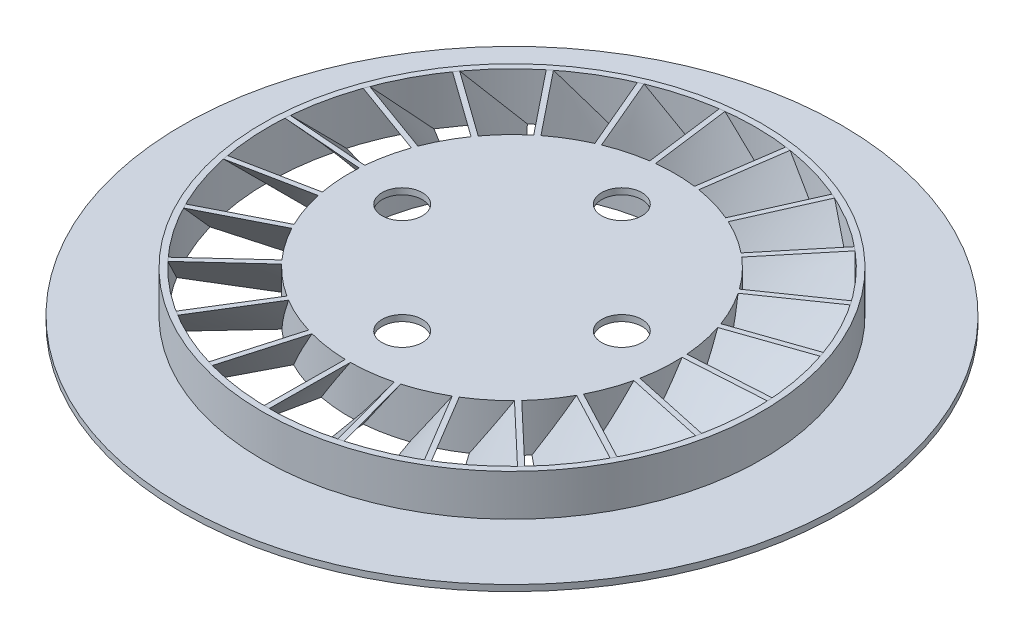
SolidWorks part; units mm, degrees
ref_plane "Front Plane" through (0, 0, 0) normal (0, 0, 1) x (1, 0, 0)
ref_plane "Top Plane" through (0, 0, 0) normal (0, 1, 0) x (1, 0, 0)
ref_plane "Right Plane" through (0, 0, 0) normal (1, 0, 0) x (0, 0, -1)
sketch "Sketch1" plane through (0, 0, 0) normal (0, 1, 0) x (1, 0, 0)
  circle A0 centre (0, 0) radius 33.25
  circle A1 centre (0, 0) radius 34.0882
  circle A2 centre (0, 0) radius 45
  circle A3 centre (0, 0) radius 22.25
  circle A4 centre (0, 0) radius 21.4118
  dimension "D1" = 66.5
  dimension "D2" = 0.8382
  dimension "D3" = 90
  dimension "D4" = 44.5
  dimension "D5" = 0.8382
extrude "Boss-Extrude1" add sketch "Sketch1" along normal blind 6.5 contours A1 A0 region at (-33.9918, 0, 0)
extrude "Boss-Extrude2" add sketch "Sketch1<3>" along normal blind 0.8382 contours A2 A1 region at (-43.7272, 0, 0)
sketch "Sketch1<3>" plane through (0, 0, 0) normal (0, 1, 0) x (1, 0, 0) same geometry as "Sketch1"
extrude "Boss-Extrude3" add sketch "Sketch1<4>" along normal blind 6.5 separate body contours A3 A4 region at (-21.6207, 0, 0)
sketch "Sketch1<4>" plane through (0, 0, 0) normal (0, 1, 0) x (1, 0, 0) same geometry as "Sketch1"
extrude "Boss-Extrude4" add sketch "Sketch1<5>" along normal blind 0.7 contours A4 region at (0, 0, 0)
sketch "Sketch1<5>" plane through (0, 0, 0) normal (0, 1, 0) x (1, 0, 0) same geometry as "Sketch1"
sketch "Sketch2" plane through (0, 0, 0) normal (0, -1, 0) x (1, 0, 0)
  line L0 (-31.9208, 9.3073) -> (-21.3278, 6.3393)
  line L1 (-33.2482, 0.35) -> (-22.2472, 0.35)
  line L2 (-33.2482, -0.35) -> (-22.2472, -0.35)
  line L3 (-32.1097, 8.6332) -> (-21.5167, 5.6652)
  line L4 (-28.226, 17.5743) -> (-18.8266, 11.8584)
  line L5 (-28.5897, 16.9762) -> (-19.1903, 11.2603)
  line L6 (-22.4378, 24.5378) -> (-14.9291, 16.498)
  line L7 (-22.9494, 24.0601) -> (-15.4407, 16.0202)
  line L8 (-14.9856, 29.6816) -> (-9.9244, 19.914)
  line L9 (-15.6071, 29.3595) -> (-10.5459, 19.592)
  line L10 (-6.4219, 32.624) -> (-4.1837, 21.8531)
  line L11 (-7.1072, 32.4815) -> (-4.869, 21.7107)
  line L12 (2.6181, 33.1468) -> (1.8674, 22.1715)
  line L13 (1.9198, 33.1945) -> (1.169, 22.2193)
  line L14 (11.4639, 31.2112) -> (7.7799, 20.8455)
  line L15 (10.8043, 31.4456) -> (7.1204, 21.0799)
  line L16 (19.4595, 26.9609) -> (13.1155, 17.9735)
  line L17 (18.8876, 27.3646) -> (12.5436, 18.3772)
  line L18 (26.0119, 20.711) -> (17.4783, 13.7685)
  line L19 (25.5701, 21.254) -> (17.0366, 14.3115)
  line L20 (30.635, 12.9251) -> (20.5449, 8.5423)
  line L21 (30.3561, 13.5671) -> (20.266, 9.1844)
  line L22 (32.9861, 4.1806) -> (22.0877, 2.6826)
  line L23 (32.8908, 4.874) -> (21.9924, 3.3761)
  line L24 (32.8908, -4.874) -> (21.9924, -3.3761)
  line L25 (32.9861, -4.1806) -> (22.0877, -2.6826)
  line L26 (30.3561, -13.5671) -> (20.266, -9.1844)
  line L27 (30.635, -12.9251) -> (20.5449, -8.5423)
  line L28 (25.5701, -21.254) -> (17.0366, -14.3115)
  line L29 (26.0119, -20.711) -> (17.4783, -13.7685)
  line L30 (18.8876, -27.3646) -> (12.5436, -18.3772)
  line L31 (19.4595, -26.9609) -> (13.1155, -17.9735)
  line L32 (10.8043, -31.4456) -> (7.1204, -21.0799)
  line L33 (11.4639, -31.2112) -> (7.7799, -20.8455)
  line L34 (1.9198, -33.1945) -> (1.169, -22.2193)
  line L35 (2.6181, -33.1468) -> (1.8674, -22.1715)
  line L36 (-7.1072, -32.4815) -> (-4.869, -21.7107)
  line L37 (-6.4219, -32.624) -> (-4.1837, -21.8531)
  line L38 (-15.6071, -29.3595) -> (-10.5459, -19.592)
  line L39 (-14.9856, -29.6816) -> (-9.9244, -19.914)
  line L40 (-22.9494, -24.0601) -> (-15.4407, -16.0202)
  line L41 (-22.4378, -24.5378) -> (-14.9291, -16.498)
  line L42 (-28.5897, -16.9762) -> (-19.1903, -11.2603)
  line L43 (-28.226, -17.5743) -> (-18.8266, -11.8584)
  line L44 (-32.1097, -8.6332) -> (-21.5167, -5.6652)
  line L45 (-31.9208, -9.3073) -> (-21.3278, -6.3393)
  circle A0 centre (0, 0) radius 33.25 construction
  circle A1 centre (0, 0) radius 22.25
  arc A2 (-21.3278, 6.3393) -> (-21.5167, 5.6652) centre (0, 0) ccw
  arc A3 (-18.8266, 11.8584) -> (-19.1903, 11.2603) centre (0, 0) ccw
  circle A5 centre (0, 0) radius 22.25 construction
  arc A6 (-31.9208, 9.3073) -> (-32.1097, 8.6332) centre (0, 0) ccw
  arc A7 (-28.226, 17.5743) -> (-28.5897, 16.9762) centre (0, 0) ccw
  arc A8 (-22.4378, 24.5378) -> (-22.9494, 24.0601) centre (0, 0) ccw
  arc A9 (-14.9291, 16.498) -> (-15.4407, 16.0202) centre (0, 0) ccw
  arc A10 (-9.9244, 19.914) -> (-10.5459, 19.592) centre (0, 0) ccw
  arc A11 (-14.9856, 29.6816) -> (-15.6071, 29.3595) centre (0, 0) ccw
  arc A12 (-6.4219, 32.624) -> (-7.1072, 32.4815) centre (0, 0) ccw
  arc A13 (-4.1837, 21.8531) -> (-4.869, 21.7107) centre (0, 0) ccw
  arc A14 (1.8674, 22.1715) -> (1.169, 22.2193) centre (0, 0) ccw
  arc A15 (2.6181, 33.1468) -> (1.9198, 33.1945) centre (0, 0) ccw
  arc A16 (11.4639, 31.2112) -> (10.8043, 31.4456) centre (0, 0) ccw
  arc A17 (7.7799, 20.8455) -> (7.1204, 21.0799) centre (0, 0) ccw
  arc A18 (13.1155, 17.9735) -> (12.5436, 18.3772) centre (0, 0) ccw
  arc A19 (19.4595, 26.9609) -> (18.8876, 27.3646) centre (0, 0) ccw
  arc A20 (26.0119, 20.711) -> (25.5701, 21.254) centre (0, 0) ccw
  arc A21 (17.4783, 13.7685) -> (17.0366, 14.3115) centre (0, 0) ccw
  arc A22 (20.5449, 8.5423) -> (20.266, 9.1844) centre (0, 0) ccw
  arc A23 (30.635, 12.9251) -> (30.3561, 13.5671) centre (0, 0) ccw
  arc A24 (32.9861, 4.1806) -> (32.8908, 4.874) centre (0, 0) ccw
  arc A25 (22.0877, 2.6826) -> (21.9924, 3.3761) centre (0, 0) ccw
  arc A26 (21.9924, -3.3761) -> (22.0877, -2.6826) centre (0, 0) ccw
  arc A27 (32.8908, -4.874) -> (32.9861, -4.1806) centre (0, 0) ccw
  arc A28 (-22.2472, 0.35) -> (-22.2472, -0.35) centre (0, 0) ccw
  arc A29 (-33.2482, 0.35) -> (-33.2482, -0.35) centre (0, 0) ccw
  arc A30 (-21.5167, -5.6652) -> (-21.3278, -6.3393) centre (0, 0) ccw
  arc A31 (-32.1097, -8.6332) -> (-31.9208, -9.3073) centre (0, 0) ccw
  arc A32 (-19.1903, -11.2603) -> (-18.8266, -11.8584) centre (0, 0) ccw
  arc A33 (-28.5897, -16.9762) -> (-28.226, -17.5743) centre (0, 0) ccw
  arc A34 (-22.9494, -24.0601) -> (-22.4378, -24.5378) centre (0, 0) ccw
  arc A35 (-15.4407, -16.0202) -> (-14.9291, -16.498) centre (0, 0) ccw
  arc A36 (-10.5459, -19.592) -> (-9.9244, -19.914) centre (0, 0) ccw
  arc A37 (-15.6071, -29.3595) -> (-14.9856, -29.6816) centre (0, 0) ccw
  arc A38 (-7.1072, -32.4815) -> (-6.4219, -32.624) centre (0, 0) ccw
  arc A39 (-4.869, -21.7107) -> (-4.1837, -21.8531) centre (0, 0) ccw
  arc A40 (1.169, -22.2193) -> (1.8674, -22.1715) centre (0, 0) ccw
  arc A41 (1.9198, -33.1945) -> (2.6181, -33.1468) centre (0, 0) ccw
  arc A42 (10.8043, -31.4456) -> (11.4639, -31.2112) centre (0, 0) ccw
  arc A43 (7.1204, -21.0799) -> (7.7799, -20.8455) centre (0, 0) ccw
  arc A44 (12.5436, -18.3772) -> (13.1155, -17.9735) centre (0, 0) ccw
  arc A45 (18.8876, -27.3646) -> (19.4595, -26.9609) centre (0, 0) ccw
  arc A46 (25.5701, -21.254) -> (26.0119, -20.711) centre (0, 0) ccw
  arc A47 (17.0366, -14.3115) -> (17.4783, -13.7685) centre (0, 0) ccw
  arc A48 (20.266, -9.1844) -> (20.5449, -8.5423) centre (0, 0) ccw
  arc A49 (30.3561, -13.5671) -> (30.635, -12.9251) centre (0, 0) ccw
  point P106 (0, 0)
  dimension "D3" = 0.7
  dimension "D1" = 0
  dimension "D4" = 23
sketch "Sketch3" plane through (0, 6.5, 0) normal (0, 1, 0) x (1, 0, 0)
  line L0 (0, 0) -> (-32.6054, -6.5152) construction
  line L1 (0, 0) -> (-15.6581, 0) construction
  line L2 (-21.8846, -4.016) -> (-32.6722, -6.1716)
  line L3 (-21.7474, -4.7025) -> (-32.535, -6.8581)
  line L4 (-22.1565, 2.0373) -> (-33.1257, 2.8721)
  line L5 (-22.2097, 1.3393) -> (-33.1788, 2.1741)
  line L6 (-20.7853, 7.9395) -> (-31.1225, 11.7028)
  line L7 (-21.0247, 7.2817) -> (-31.3619, 11.045)
  line L8 (-17.8724, 13.2529) -> (-26.811, 19.6656)
  line L9 (-18.2805, 12.6841) -> (-27.219, 19.0968)
  line L10 (-13.6341, 17.5833) -> (-20.511, 26.1698)
  line L11 (-14.1805, 17.1457) -> (-21.0574, 25.7322)
  line L12 (-8.3846, 20.6097) -> (-12.6899, 30.7332)
  line L13 (-9.0288, 20.3358) -> (-13.3341, 30.4592)
  line L14 (-2.5132, 22.1076) -> (-3.9276, 33.0172)
  line L15 (-3.2074, 22.0176) -> (-4.6218, 32.9272)
  line L16 (3.5445, 21.9659) -> (5.126, 32.8525)
  line L17 (2.8518, 22.0665) -> (4.4332, 32.9531)
  line L18 (9.3394, 20.195) -> (13.7994, 30.2513)
  line L19 (8.6995, 20.4788) -> (13.1595, 30.5351)
  line L20 (14.4416, 16.9264) -> (21.4494, 25.4064)
  line L21 (13.902, 17.3723) -> (20.9098, 25.8524)
  line L22 (18.4728, 12.4024) -> (27.5085, 18.6773)
  line L23 (18.0735, 12.9774) -> (27.1093, 19.2523)
  line L24 (21.1339, 6.9586) -> (31.5275, 10.563)
  line L25 (20.9045, 7.6199) -> (31.2982, 11.2244)
  line L26 (22.2276, 0.9987) -> (33.2083, 1.6653)
  line L27 (22.1852, 1.6974) -> (33.1659, 2.364)
  line L28 (21.6728, -5.0353) -> (32.4261, -7.356)
  line L29 (21.8204, -4.351) -> (32.5738, -6.6717)
  line L30 (19.5106, -10.6958) -> (29.239, -15.8316)
  line L31 (19.8374, -10.0768) -> (29.5658, -15.2126)
  line L32 (15.9014, -15.563) -> (23.8835, -23.1332)
  line L33 (16.3831, -15.0551) -> (24.3652, -22.6252)
  line L34 (11.1129, -19.2761) -> (16.7565, -28.719)
  line L35 (11.7137, -18.917) -> (17.3574, -28.3599)
  line L36 (5.5001, -21.5595) -> (8.3869, -32.1749)
  line L37 (6.1756, -21.3758) -> (9.0623, -31.9912)
  line L38 (-0.5205, -22.2439) -> (-0.6048, -33.2445)
  line L39 (0.1795, -22.2493) -> (0.0952, -33.2499)
  line L40 (-6.5025, -21.2786) -> (-9.5516, -31.8485)
  line L41 (-5.83, -21.4726) -> (-8.8791, -32.0425)
  line L42 (-12.0023, -18.7352) -> (-17.7901, -28.0905)
  line L43 (-11.407, -19.1035) -> (-17.1948, -28.4588)
  line L44 (-16.6119, -14.8023) -> (-24.7091, -22.2491)
  line L45 (-16.1381, -15.3175) -> (-24.2352, -22.7644)
  line L46 (-19.9895, -9.7715) -> (-29.7956, -14.7576)
  line L47 (-19.6722, -10.3955) -> (-29.4783, -15.3816)
  circle A0 centre (0, 0) radius 33.25 construction
  circle A1 centre (0, 0) radius 22.25 construction
  arc A2 (-32.6722, -6.1716) -> (-32.535, -6.8581) centre (0, 0) ccw
  arc A3 (-21.8846, -4.016) -> (-21.7474, -4.7025) centre (0, 0) ccw
  arc A4 (-22.1565, 2.0373) -> (-22.2097, 1.3393) centre (0, 0) ccw
  arc A5 (-33.1257, 2.8721) -> (-33.1788, 2.1741) centre (0, 0) ccw
  arc A6 (-20.7853, 7.9395) -> (-21.0247, 7.2817) centre (0, 0) ccw
  arc A7 (-31.1225, 11.7028) -> (-31.3619, 11.045) centre (0, 0) ccw
  arc A8 (-17.8724, 13.2529) -> (-18.2805, 12.6841) centre (0, 0) ccw
  arc A9 (-26.811, 19.6656) -> (-27.219, 19.0968) centre (0, 0) ccw
  arc A10 (-13.6341, 17.5833) -> (-14.1805, 17.1457) centre (0, 0) ccw
  arc A11 (-20.511, 26.1698) -> (-21.0574, 25.7322) centre (0, 0) ccw
  arc A12 (-8.3846, 20.6097) -> (-9.0288, 20.3358) centre (0, 0) ccw
  arc A13 (-12.6899, 30.7332) -> (-13.3341, 30.4592) centre (0, 0) ccw
  arc A14 (-2.5132, 22.1076) -> (-3.2074, 22.0176) centre (0, 0) ccw
  arc A15 (-3.9276, 33.0172) -> (-4.6218, 32.9272) centre (0, 0) ccw
  arc A16 (3.5445, 21.9659) -> (2.8518, 22.0665) centre (0, 0) ccw
  arc A17 (5.126, 32.8525) -> (4.4332, 32.9531) centre (0, 0) ccw
  arc A18 (9.3394, 20.195) -> (8.6995, 20.4788) centre (0, 0) ccw
  arc A19 (13.7994, 30.2513) -> (13.1595, 30.5351) centre (0, 0) ccw
  arc A20 (14.4416, 16.9264) -> (13.902, 17.3723) centre (0, 0) ccw
  arc A21 (21.4494, 25.4064) -> (20.9098, 25.8524) centre (0, 0) ccw
  arc A22 (18.4728, 12.4024) -> (18.0735, 12.9774) centre (0, 0) ccw
  arc A23 (27.5085, 18.6773) -> (27.1093, 19.2523) centre (0, 0) ccw
  arc A24 (21.1339, 6.9586) -> (20.9045, 7.6199) centre (0, 0) ccw
  arc A25 (31.5275, 10.563) -> (31.2982, 11.2244) centre (0, 0) ccw
  arc A26 (22.2276, 0.9987) -> (22.1852, 1.6974) centre (0, 0) ccw
  arc A27 (33.2083, 1.6653) -> (33.1659, 2.364) centre (0, 0) ccw
  arc A28 (21.6728, -5.0353) -> (21.8204, -4.351) centre (0, 0) ccw
  arc A29 (32.4261, -7.356) -> (32.5738, -6.6717) centre (0, 0) ccw
  arc A30 (19.5106, -10.6958) -> (19.8374, -10.0768) centre (0, 0) ccw
  arc A31 (29.239, -15.8316) -> (29.5658, -15.2126) centre (0, 0) ccw
  arc A32 (15.9014, -15.563) -> (16.3831, -15.0551) centre (0, 0) ccw
  arc A33 (23.8835, -23.1332) -> (24.3652, -22.6252) centre (0, 0) ccw
  arc A34 (11.1129, -19.2761) -> (11.7137, -18.917) centre (0, 0) ccw
  arc A35 (16.7565, -28.719) -> (17.3574, -28.3599) centre (0, 0) ccw
  arc A36 (5.5001, -21.5595) -> (6.1756, -21.3758) centre (0, 0) ccw
  arc A37 (8.3869, -32.1749) -> (9.0623, -31.9912) centre (0, 0) ccw
  arc A38 (-0.5205, -22.2439) -> (0.1795, -22.2493) centre (0, 0) ccw
  arc A39 (-0.6048, -33.2445) -> (0.0952, -33.2499) centre (0, 0) ccw
  arc A40 (-6.5025, -21.2786) -> (-5.83, -21.4726) centre (0, 0) ccw
  arc A41 (-9.5516, -31.8485) -> (-8.8791, -32.0425) centre (0, 0) ccw
  arc A42 (-12.0023, -18.7352) -> (-11.407, -19.1035) centre (0, 0) ccw
  arc A43 (-17.7901, -28.0905) -> (-17.1948, -28.4588) centre (0, 0) ccw
  arc A44 (-16.6119, -14.8023) -> (-16.1381, -15.3175) centre (0, 0) ccw
  arc A45 (-24.7091, -22.2491) -> (-24.2352, -22.7644) centre (0, 0) ccw
  arc A46 (-19.9895, -9.7715) -> (-19.6722, -10.3955) centre (0, 0) ccw
  arc A47 (-29.7956, -14.7576) -> (-29.4783, -15.3816) centre (0, 0) ccw
  point P101 (0, 0)
  dimension "D1" = 11.3
  dimension "D2" = 0.35
  dimension "D3" = 0.35
  dimension "D4" = 23
loft "Loft1" add section "Sketch2" section "Sketch3" connector at (-32.1097, 0, 8.6332) connector at (-29.7956, 6.5, 14.7576)
pattern_circular "CirPattern1" count 23 over 360 about axis through (0, 6.5, 0) along (0, -1, 0) of "Loft1"
sketch "Sketch4" plane through (0, 6.5, 0) normal (0, 1, 0) x (1, 0, 0)
  circle A0 centre (0, 0) radius 21.55
  dimension "D1" = 43.1
extrude "Boss-Extrude5" add sketch "Sketch4" against normal blind 0.8382
sketch "Sketch6" plane through (0, 0, 0) normal (0, -1, 0) x (1, 0, 0)
  line L0 (0, 0) -> (0, 14.9949) construction
  line L1 (0, 0) -> (14.9949, 0) construction
  line L2 (0, 0) -> (0, -14.9949) construction
  line L3 (0, 0) -> (-14.9949, 0) construction
  point P9 (0, 0)
  dimension "D1" = 14.9949
  dimension "D2" = 4
hole_wizard "CBORE for M5 Hex Head Bolt1" positions "3DSketch4" profile "Sketch7" counterbore size "M5" standard "ANSI Metric" end condition through all
sketch3d "3DSketch4"
  point P0 (0, 0, 14.9949)
  point P3 (14.9949, 0, 0)
  point P6 (0, 0, -14.9949)
  point P9 (-14.9949, 0, 0)
sketch "Sketch7" plane through (0, 0, 14.9949) normal (1, 0, 0) x (0, 0, -1)
  line L0 (0, 0) -> (0, 6.5001)
  line L1 (0, 6.5001) -> (2.75, 6.5001)
  line L3 (2.75, 6.5001) -> (2.75, 3.58)
  line L4 (2.75, 3.58) -> (6.12, 3.58)
  line L5 (6.12, 3.58) -> (6.12, 0)
  line L7 (6.12, 0) -> (0, 0)
  line L11 (0, -6.35) -> (0, 107.95) construction
  dimension "Thru Hole Dia." = 5.5
  dimension "Thru Hole Depth" = 6.5001
  dimension "C'Bore Dia." = 12.24
  dimension "C'Bore Depth" = 3.58
sketch "Sketch8" plane through (0, 0, 0) normal (0, -1, 0) x (1, 0, 0)
  circle A0 centre (0, 0) radius 21.39
  arc A1 (22.0877, -2.6826) -> (22.0877, 2.6826) centre (0, 0) ccw construction
  circle A2 centre (0, 0) radius 22.25
  dimension "D1" = 0.86
  dimension "D2" = 44.5
extrude "Cut-Extrude1" cut sketch "Sketch8" against normal blind 1.5 contours A0 region at (0, 0, 0)
extrude "Boss-Extrude6" add sketch "Sketch8<2>" against normal up to surface (6.5 mm away) up to face at (0, 6.5, 17.7449)
sketch "Sketch8<2>" plane through (0, 0, 0) normal (0, -1, 0) x (1, 0, 0) same geometry as "Sketch8"
